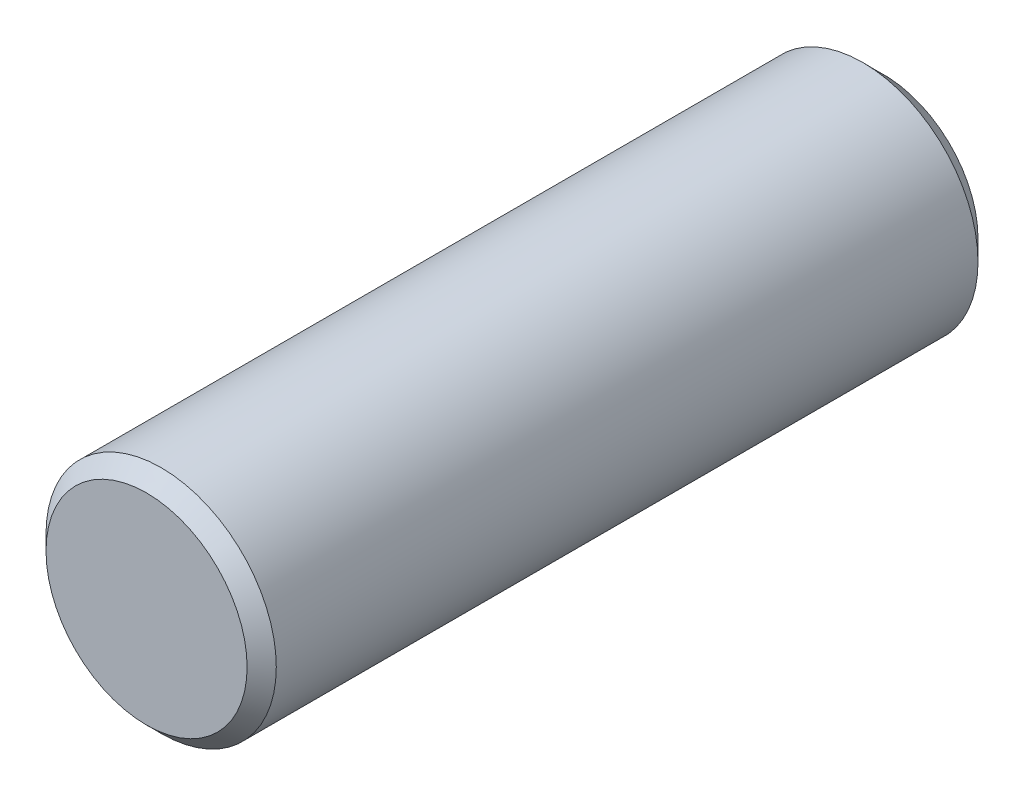
SolidWorks part; units mm, degrees
material "AISI 304"
ref_plane "Front Plane" through (0, 0, 0) normal (0, 0, 1) x (1, 0, 0)
ref_plane "Top Plane" through (0, 0, 0) normal (0, 1, 0) x (1, 0, 0)
ref_plane "Right Plane" through (0, 0, 0) normal (1, 0, 0) x (0, 0, -1)
sketch "Sketch1" plane through (0, 0, 0) normal (1, 0, 0) x (0, 0, -1)
  line L0 (-6.35, 0) -> (-6.35, 1.7329)
  line L1 (-6.35, 1.7329) -> (-6.0986, 1.9844)
  line L2 (-6.0986, 1.9844) -> (5.9944, 1.9844)
  line L3 (5.9944, 1.9844) -> (6.35, 1.6288)
  line L4 (6.35, 1.6288) -> (6.35, 0)
  line L5 (6.35, 0) -> (-6.35, 0)
  line L6 (6.35, 0) -> (-6.35, 0) construction
revolve "Revolve1" add sketch "Sketch1" angle 360 about L6 reverse direction yes
ref_plane "dia1 XY" through (0, 0, 0) normal (0, 0, 1) x (1, 0, 0)
ref_plane "dia1 XZ" through (0, 0, 0) normal (0, -1, 0) x (-1, 0, 0)
ref_plane "dia1 YZ" through (-1.9844, 0, 0) normal (1, 0, 0) x (0, 0, -1)
ref_axis "dia1 X" through (-80.9, 0, 0) along (1, 0, 0)
ref_axis "dia1 Y" through (-1.9844, -50, 0) along (0, 1, 0)
ref_axis "dia1 Z" through (-1.9844, 0, 80.9) along (0, 0, -1)
sketch3d "dia1"
  point P0 (-1.9844, 0, 0)
ref_plane "dia2 XY" through (0, 0, 0) normal (0, 0, 1) x (1, 0, 0)
ref_plane "dia2 XZ" through (0, 0, 0) normal (0, -1, 0) x (-1, 0, 0)
ref_plane "dia2 YZ" through (1.9844, 0, 0) normal (1, 0, 0) x (0, 0, -1)
ref_axis "dia2 X" through (-80.9, 0, 0) along (1, 0, 0)
ref_axis "dia2 Y" through (1.9844, -50, 0) along (0, 1, 0)
ref_axis "dia2 Z" through (1.9844, 0, 80.9) along (0, 0, -1)
sketch3d "dia2"
  point P0 (1.9844, 0, 0)
ref_plane "pin XY" through (0, 0, 0) normal (0, 0, 1) x (1, 0, 0)
ref_plane "pin XZ" through (0, 0, 0) normal (0, -1, 0) x (-1, 0, 0)
ref_plane "pin YZ" through (0, 0, 0) normal (1, 0, 0) x (0, 0, -1)
ref_axis "pin X" through (-80.9, 0, 0) along (1, 0, 0)
ref_axis "pin Y" through (0, -50, 0) along (0, 1, 0)
ref_axis "pin Z" through (0, 0, 80.9) along (0, 0, -1)
sketch3d "pin"
  point P0 (0, 0, 0)
ref_plane "pin1 XY" through (0, 0, 0) normal (1, 0, 0) x (0, 0, -1)
ref_plane "pin1 XZ" through (0, 0, 0) normal (0, -1, 0) x (-1, 0, 0)
ref_plane "pin1 YZ" through (0, 0, 6.35) normal (0, 0, -1) x (-1, 0, 0)
ref_axis "pin1 X" through (0, 0, 80.9) along (0, 0, -1)
ref_axis "pin1 Y" through (0, -50, 6.35) along (0, 1, 0)
ref_axis "pin1 Z" through (80.9, 0, 6.35) along (-1, 0, 0)
sketch3d "pin1"
  point P0 (0, 0, 6.35)
ref_plane "pin2 XY" through (0, 0, 0) normal (1, 0, 0) x (0, 0, -1)
ref_plane "pin2 XZ" through (0, 0, 0) normal (0, -1, 0) x (-1, 0, 0)
ref_plane "pin2 YZ" through (0, 0, -6.35) normal (0, 0, -1) x (-1, 0, 0)
ref_axis "pin2 X" through (0, 0, 80.9) along (0, 0, -1)
ref_axis "pin2 Y" through (0, -50, -6.35) along (0, 1, 0)
ref_axis "pin2 Z" through (80.9, 0, -6.35) along (-1, 0, 0)
sketch3d "pin2"
  point P0 (0, 0, -6.35)
